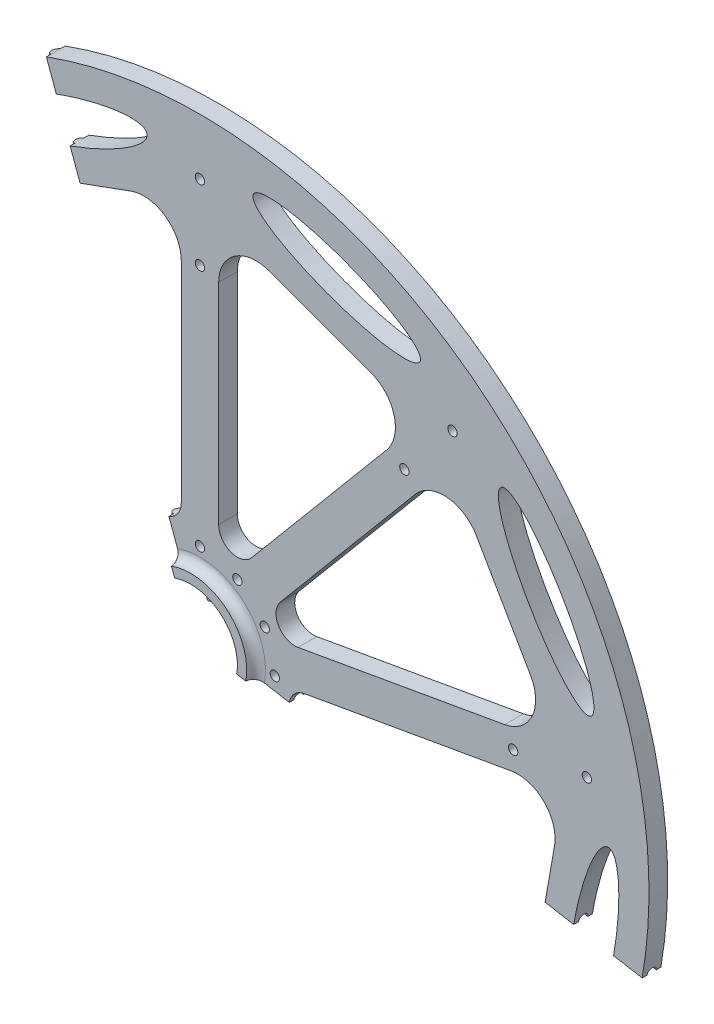
SolidWorks part; units mm, degrees
ref_plane "Front Plane" through (0, 0, 0) normal (0, 0, 1) x (1, 0, 0)
ref_plane "Top Plane" through (0, 0, 0) normal (0, 1, 0) x (1, 0, 0)
ref_plane "Right Plane" through (0, 0, 0) normal (1, 0, 0) x (0, 0, -1)
sketch "Sketch1" plane through (0, 0, 0) normal (0, 0, 1) x (1, 0, 0)
  line L0 (0, 146.05) -> (0, 152.4) construction
  line L1 (-12.7, 146.05) -> (12.7, 146.05) construction
  line L2 (-12.7, 146.05) -> (-12.7, 95.25) construction
  line L3 (-12.7, 95.25) -> (12.7, 95.25) construction
  line L4 (12.7, 146.05) -> (12.7, 95.25) construction
  line L5 (-12.7, 120.65) -> (12.7, 120.65) construction
  line L6 (0, 95.25) -> (0, 120.65) construction
  line L7 (0, 120.65) -> (0, 146.05) construction
  line L8 (0, 0) -> (0, 25.4) construction
  line L9 (150.0847, -26.464) -> (6.2307, -1.0986)
  line L10 (-2.1639, 5.9452) -> (-52.1239, 143.2092)
  line L11 (0, 0) -> (0, 25.4) construction
  line L12 (0, 0) -> (12.7, 21.997) construction
  arc A0 (150.0847, -26.464) -> (-52.1239, 143.2092) centre (0, 0) ccw
  circle A1 centre (0, 0) radius 146.05 construction
  circle A2 centre (0, 133.35) radius 1.5875
  circle A3 centre (0, 107.95) radius 1.5875
  circle A4 centre (85.7157, 102.152) radius 1.5875
  circle A5 centre (69.3889, 82.6945) radius 1.5875
  circle A6 centre (131.3241, 23.156) radius 1.5875
  circle A7 centre (106.31, 18.7453) radius 1.5875
  circle A20 centre (-115.4845, -66.675) radius 1.5875 [skipped]
  circle A21 centre (-93.4874, -53.975) radius 1.5875 [skipped]
  circle A22 centre (-131.3241, 23.156) radius 1.5875 [skipped]
  circle A23 centre (-106.31, 18.7453) radius 1.5875 [skipped]
  circle A24 centre (-85.7157, 102.152) radius 1.5875 [skipped]
  circle A25 centre (-69.3889, 82.6945) radius 1.5875 [skipped]
  circle A26 centre (115.4845, -66.675) radius 1.5875 [skipped]
  circle A27 centre (93.4874, -53.975) radius 1.5875 [skipped]
  circle A28 centre (45.6084, -125.308) radius 1.5875 [skipped]
  circle A29 centre (36.9211, -101.4398) radius 1.5875 [skipped]
  circle A30 centre (-45.6084, -125.308) radius 1.5875 [skipped]
  circle A31 centre (-36.9211, -101.4398) radius 1.5875 [skipped]
  arc A32 (6.2307, -1.0986) -> (-2.1639, 5.9452) centre (0, 0) ccw
  circle A33 centre (0, 0) radius 25.4 construction
  circle A34 centre (0, 25.4) radius 1.5875
  circle A35 centre (12.7, 21.997) radius 1.5875
  circle A36 centre (21.997, 12.7) radius 1.5875
  circle A37 centre (25.4, 0) radius 1.5875
  point P9 (0, 146.05)
  point P52 (0, 0)
  dimension "D1" = 304.8
  dimension "D2" = 292.1
  dimension "D5" = 3.175
  dimension "D6" = 9
  dimension "D7" = 178.864
  dimension "D8" = 50.8
  dimension "D9" = 3.175
  dimension "D3" = 25.4
  dimension "D4" = 50.8
  dimension "D11" = 30
  dimension "D10" = 4
extrude "Boss-Extrude1" add sketch "Sketch1" along normal blind 6.35
ref_plane "Plane1" through (-52.1239, 143.2092, 0) normal (-0.342, 0.9397, 0) x (0, 0, -1)
sketch "Sketch2" plane through (-52.1239, 143.2092, 0) normal (-0.342, 0.9397, 0) x (0, 0, -1)
  line L0 (-6.35, 0) -> (0, 0) construction
  line L1 (-4.7625, 0) -> (-1.5875, 0)
  arc A0 (-15319.5887, -4174.0982) -> (15871.5688, 90.1844) centre (-3.175, 0) cw
  arc A1 (-4.7625, 0) -> (-1.5875, 0) centre (-3.175, 0) cw
  dimension "D1" = 1.5875
  dimension "D2" = 3.175
extrude "Boss-Extrude2" add sketch "Sketch2" against normal blind 133.35 contours A1 L1 region at (-52.757, 142.9787, 3.175)
ref_plane "Plane2" through (150.0847, -26.464, 0) normal (-0.9848, 0.1736, 0) x (0, 0, -1)
sketch "Sketch3" plane through (150.0847, -26.464, 0) normal (-0.9848, 0.1736, 0) x (0, 0, -1)
  line L0 (-6.35, 0) -> (0, 0) construction
  line L1 (-4.7625, 0) -> (-1.5875, 0)
  arc A0 (-4.7625, 0) -> (-1.5875, 0) centre (-3.175, 0) ccw
  dimension "D1" = 3.175
extrude "Cut-Extrude1" cut sketch "Sketch3" along normal blind 133.35 contours L1 A0
sketch "Sketch5" plane through (0, 0, 6.35) normal (0, 0, 1) x (1, 0, 0)
  line L0 (0, 133.35) -> (0, 0) construction
  line L1 (0, 0) -> (85.7157, 102.152) construction
  line L2 (85.7157, 102.152) -> (0, 133.35) construction
  line L3 (57.9784, 105.4901) -> (23.3937, 118.0779)
  line L4 (6.35, 106.1438) -> (6.35, 34.893)
  line L5 (17.5644, 30.8113) -> (63.3635, 85.3926)
  line L6 (6.35, 17.4465) -> (75.0221, 99.2867) construction
  line L7 (75.0221, 99.2867) -> (6.35, 124.2813) construction
  line L8 (6.35, 124.2813) -> (6.35, 17.4465) construction
  line L9 (40.686, 111.784) -> (52.1239, 143.2092) construction
  line L10 (112.2217, 43.5423) -> (93.8196, 75.4157)
  line L11 (73.0923, 77.2292) -> (27.2931, 22.6479)
  line L12 (33.2602, 12.3126) -> (103.4286, 24.6852)
  line L13 (113.9553, -38.7794) -> (120.3463, -2.5342)
  line L14 (105.6339, 12.1781) -> (35.4655, -0.1944)
  line L15 (33.3932, -11.9472) -> (95.0982, -47.5726)
  line L16 (62.3679, -102.9558) -> (90.5616, -79.2984)
  line L17 (88.7482, -58.5712) -> (27.0432, -22.9457)
  line L18 (17.9011, -30.6168) -> (42.2704, -97.5707)
  line L19 (-18.4022, -118.958) -> (18.4022, -118.958)
  line L20 (30.3363, -101.9144) -> (5.967, -34.9605)
  line L21 (-5.967, -34.9605) -> (-30.3363, -101.9144)
  line L22 (-90.5616, -79.2984) -> (-62.3679, -102.9558)
  line L23 (-42.2704, -97.5707) -> (-17.9011, -30.6168)
  line L24 (-27.0432, -22.9457) -> (-88.7482, -58.5712)
  line L25 (-120.3463, -2.5342) -> (-113.9553, -38.7794)
  line L26 (-95.0982, -47.5726) -> (-33.3932, -11.9472)
  line L27 (-35.4655, -0.1944) -> (-105.6339, 12.1781)
  line L28 (-93.8196, 75.4157) -> (-112.2217, 43.5423)
  line L29 (-103.4286, 24.6852) -> (-33.2602, 12.3126)
  line L30 (-27.2931, 22.6479) -> (-73.0923, 77.2292)
  line L31 (-23.3937, 118.0779) -> (-57.9784, 105.4901)
  line L32 (-63.3635, 85.3926) -> (-17.5644, 30.8113)
  line L33 (-6.35, 34.893) -> (-6.35, 106.1438)
  line L34 (0, 0) -> (17.5644, 30.8113) construction
  line L35 (0, 0) -> (33.2602, 12.3126) construction
  arc A0 (63.3635, 85.3926) -> (57.9784, 105.4901) centre (53.6348, 93.556) ccw
  arc A1 (6.35, 106.1438) -> (23.3937, 118.0779) centre (19.05, 106.1438) cw
  arc A2 (17.5644, 30.8113) -> (6.35, 34.893) centre (12.7, 34.893) cw
  arc A3 (150.0847, -26.464) -> (-52.1239, 143.2092) centre (0, 0) ccw construction
  arc A4 (73.0923, 77.2292) -> (93.8196, 75.4157) centre (82.8211, 69.0657) cw
  arc A5 (103.4286, 24.6852) -> (112.2217, 43.5423) centre (101.2232, 37.1923) ccw
  arc A6 (33.2602, 12.3126) -> (27.2931, 22.6479) centre (32.1575, 18.5662) cw
  arc A7 (105.6339, 12.1781) -> (120.3463, -2.5342) centre (107.8392, -0.3289) cw
  arc A8 (95.0982, -47.5726) -> (113.9553, -38.7794) centre (101.4482, -36.5741) ccw
  arc A9 (33.3932, -11.9472) -> (35.4655, -0.1944) centre (36.5682, -6.448) cw
  arc A10 (88.7482, -58.5712) -> (90.5616, -79.2984) centre (82.3982, -69.5697) cw
  arc A11 (42.2704, -97.5707) -> (62.3679, -102.9558) centre (54.2045, -93.227) ccw
  arc A12 (17.9011, -30.6168) -> (27.0432, -22.9457) centre (23.8682, -28.445) cw
  arc A13 (30.3363, -101.9144) -> (18.4022, -118.958) centre (18.4022, -106.258) cw
  arc A14 (-30.3363, -101.9144) -> (-18.4022, -118.958) centre (-18.4022, -106.258) ccw
  arc A15 (-5.967, -34.9605) -> (5.967, -34.9605) centre (0, -37.1323) cw
  arc A16 (-42.2704, -97.5707) -> (-62.3679, -102.9558) centre (-54.2045, -93.227) cw
  arc A17 (-88.7482, -58.5712) -> (-90.5616, -79.2984) centre (-82.3982, -69.5697) ccw
  arc A18 (-27.0432, -22.9457) -> (-17.9011, -30.6168) centre (-23.8682, -28.445) cw
  arc A19 (-95.0982, -47.5726) -> (-113.9553, -38.7794) centre (-101.4482, -36.5741) cw
  arc A20 (-105.6339, 12.1781) -> (-120.3463, -2.5342) centre (-107.8392, -0.3289) ccw
  arc A21 (-35.4655, -0.1944) -> (-33.3932, -11.9472) centre (-36.5682, -6.448) cw
  arc A22 (-103.4286, 24.6852) -> (-112.2217, 43.5423) centre (-101.2232, 37.1923) cw
  arc A23 (-73.0923, 77.2292) -> (-93.8196, 75.4157) centre (-82.8211, 69.0657) ccw
  arc A24 (-27.2931, 22.6479) -> (-33.2602, 12.3126) centre (-32.1575, 18.5662) cw
  arc A25 (-63.3635, 85.3926) -> (-57.9784, 105.4901) centre (-53.6348, 93.556) cw
  arc A26 (-6.35, 106.1438) -> (-23.3937, 118.0779) centre (-19.05, 106.1438) ccw
  arc A27 (-6.35, 34.893) -> (-17.5644, 30.8113) centre (-12.7, 34.893) cw
  ellipse E0 centre (46.405, 127.4966) end of major axis (18.0605, 137.8131) minor radius 6.8707
  ellipse E1 centre (117.5015, 67.8395) end of major axis (132.5832, 41.7171) minor radius 6.8707
  ellipse E2 centre (133.6177, -23.5604) end of major axis (128.3799, -53.2657) minor radius 6.8707
  ellipse E3 centre (87.2128, -103.9361) end of major axis (64.1062, -123.3249) minor radius 6.8707
  ellipse E4 centre (0, -135.679) end of major axis (-30.1635, -135.679) minor radius 6.8707
  ellipse E5 centre (-87.2128, -103.9361) end of major axis (-110.3194, -84.5474) minor radius 6.8707
  ellipse E6 centre (-133.6177, -23.5604) end of major axis (-138.8556, 6.1449) minor radius 6.8707
  ellipse E7 centre (-117.5015, 67.8395) end of major axis (-102.4197, 93.9619) minor radius 6.8707
  ellipse E8 centre (-46.405, 127.4966) end of major axis (-18.0605, 137.8131) minor radius 6.8707
  dimension "D2" = 12.7
  dimension "D3" = 6.35
  dimension "D1" = 6.35
  dimension "D4" = 9
  dimension "D5" = 40
extrude "Cut-Extrude2" cut sketch "Sketch5" against normal through all
sketch "Sketch6" plane through (0, 0, 6.35) normal (0, 0, 1) x (1, 0, 0)
  line L0 (6.2307, -1.0986) -> (30.3147, -5.3453) construction
  line L1 (-10.5282, 28.9259) -> (-2.1639, 5.9452) construction
  line L2 (6.2307, -1.0986) -> (18.7606, -3.308)
  line L3 (-6.5155, 17.9011) -> (-2.1639, 5.9452)
  arc A0 (18.7606, -3.308) -> (-6.5155, 17.9011) centre (0, 0) ccw
  arc A1 (6.2307, -1.0986) -> (-2.1639, 5.9452) centre (0, 0) ccw construction
  arc A2 (6.2307, -1.0986) -> (-2.1639, 5.9452) centre (0, 0) ccw
  dimension "D1" = 38.1
extrude "Boss-Extrude3" add sketch "Sketch6" along normal blind 3.175
sketch "Sketch7" plane through (0, 0, 9.525) normal (0, 0, 1) x (1, 0, 0)
  line L0 (6.2307, -1.0986) -> (18.7606, -3.308) construction
  line L1 (-6.5155, 17.9011) -> (-2.1639, 5.9452) construction
  line L2 (6.2307, -1.0986) -> (15.6338, -2.7567)
  line L3 (-5.4296, 14.9176) -> (-2.1639, 5.9452)
  arc A0 (15.6338, -2.7567) -> (-5.4296, 14.9176) centre (0, 0) ccw
  arc A1 (6.2307, -1.0986) -> (-2.1639, 5.9452) centre (0, 0) ccw construction
  arc A2 (6.2307, -1.0986) -> (-2.1639, 5.9452) centre (0, 0) ccw
  dimension "D1" = 31.75
extrude "Cut-Extrude3" cut sketch "Sketch7" against normal blind 7.9375
fillet "Fillet1" radius 3.175 1 edges at (12.2451, 14.5931, 6.35)
